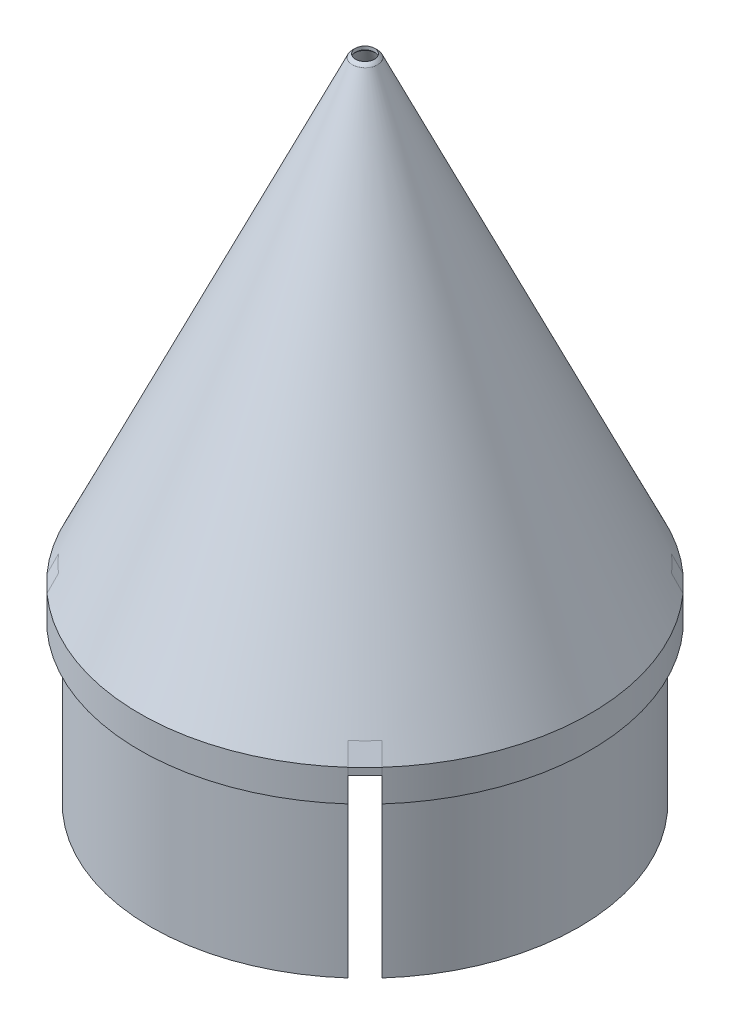
SolidWorks part; units mm, degrees
ref_plane "Front Plane" through (0, 0, 0) normal (0, 0, 1) x (1, 0, 0)
ref_plane "Top Plane" through (0, 0, 0) normal (0, 1, 0) x (1, 0, 0)
ref_plane "Right Plane" through (0, 0, 0) normal (1, 0, 0) x (0, 0, -1)
sketch "Sketch3" plane through (0, 0, 0) normal (0, 0, 1) x (1, 0, 0)
  line L1 (0, 0) -> (0, 155.682)
  line L4 (0, 0) -> (0, -50)
  line L5 (0, -50) -> (67.5, -50)
  line L6 (67.5, -50) -> (67.5, 0)
  line L9 (71, 0) -> (71, 10)
  line L11 (67.5, 0) -> (71, 0)
  line L12 (4, 153.682) -> (71, 10)
  line L13 (0, 229.1763) -> (0, 65.794) construction
  arc A0 (0, 155.682) -> (4, 153.682) centre (0, 150.682) cw
  point P11 (67.5, -50)
  point P14 (71, 10)
  dimension "Round yDim" = 2
  dimension "Lip Height" = 10
  dimension "Shoulder Height" = 50
  dimension "Half Angle" = 25
  dimension "Shoulder Diam" = 135
  dimension "Outer Diam" = 142
  dimension "Round xDim" = 8
revolve "Revolve1" add sketch "Sketch3" angle 360 about L1
shell "Shell1" thickness 0.8 removed face at (0, -50, -67.5)
sketch "Sketch7" plane through (0, 0, 0) normal (0, 1, 0) x (1, 0, 0)
  circle A0 centre (0, 0) radius 3
  dimension "PitotHoleDiam" = 6
extrude "Cut-Extrude3" cut sketch "Sketch7" along normal through all
ref_plane "Plane1" through (0, 0, 0) normal (1, 0, 0) x (0, 0, -1)
sketch "Sketch8" plane through (0, 0, 0) normal (1, 0, 0) x (0, 0, -1)
  line L0 (-39.807, 40.9099) -> (-39.807, 20) construction
  line L1 (-44.807, 44.0901) -> (-44.807, 39.0901) construction
  line L2 (-44.807, 39.0901) -> (-39.807, 40.9099) construction
  line L3 (-39.807, 40.9099) -> (-39.807, 35.9099)
  line L4 (-44.807, 44.0901) -> (-44.807, 39.0901)
  line L5 (-44.807, 39.0901) -> (-39.807, 40.9099)
  line L6 (-39.807, 35.9099) -> (-44.807, 34.0901)
  line L7 (-44.807, 34.0901) -> (-58.8839, 34.0901)
  line L8 (-3.3116, 153.2652) -> (-70.2, 9.8226) construction
  line L9 (-58.8839, 34.0901) -> (-44.807, 64.2781)
  line L10 (-44.807, 64.2781) -> (-44.807, 44.0901)
  dimension "D1" = 5
extrude "Boss-Extrude1" add sketch "Sketch8" along normal mid plane 15
sketch "Sketch9" plane through (0, 0, 0) normal (1, 0, 0) x (0, 0, -1)
  line L0 (-44.807, 39.0901) -> (-44.807, 62.9414) construction
  line L1 (-39.807, 40.9099) -> (-44.807, 39.0901) construction
  line L2 (-39.807, 35.9099) -> (-39.807, 40.9099) construction
  line L3 (-44.807, 34.0901) -> (-39.807, 35.9099) construction
  line L5 (-44.807, 39.0901) -> (-44.807, 62.9414)
  line L6 (-39.807, 40.9099) -> (-44.807, 39.0901)
  line L7 (-39.807, 35.9099) -> (-39.807, 40.9099)
  line L8 (-44.807, 34.0901) -> (-39.807, 35.9099)
  line L9 (-58.8839, 34.0901) -> (-44.807, 34.0901)
  line L10 (-44.807, 34.0901) -> (-44.807, 39.0901) construction
  line L11 (-44.807, 62.9414) -> (-58.8839, 34.0901)
extrude "Cut-Extrude4" cut sketch "Sketch9" against normal mid plane 3.5
pattern_circular "CirPattern1" count 2 over 360 about axis through (0, 0, 0) along (0, -1, 0) of "Boss-Extrude1", "Cut-Extrude4"
ref_axis "Axis1" through (0, 0, 0) along (0, -1, 0)
ref_plane "Plane2" through (0, 0, 0) normal (0.7071, 0, 0.7071) x (0, -1, 0)
sketch "Sketch11" plane through (0, 0, 0) normal (0.7071, 0, 0.7071) x (0, -1, 0)
  line L0 (-12.58, 59.0623) -> (-16.4367, 63.6586) construction
  line L1 (-16.4367, 63.6586) -> (-1.1158, 76.5143) construction
  line L2 (-1.1158, 76.5143) -> (2.7409, 71.9181) construction
  line L3 (2.7409, 71.9181) -> (-12.58, 59.0623) construction
  line L4 (-14.5083, 61.3604) -> (0.8126, 74.2162) construction
  line L5 (-8.0805, 66.7) -> (-0.8, 66.7) construction
  line L6 (-15.3609, 53.7) -> (-15.3609, 67.3869)
  line L7 (-15.3609, 67.3869) -> (-9.8226, 70.2)
  line L8 (-8.0805, 53.7) -> (-13.9678, 65.2905) construction
  line L9 (-13.9678, 65.2905) -> (-15.0999, 67.5194) construction
  line L10 (-9.8226, 70.2) -> (-153.9335, -3) construction
  line L11 (-9.8226, 70.2) -> (-0.8, 70.2)
  line L15 (0, 0) -> (50, 0) construction
  line L16 (-0.8, 53.7) -> (-0.8, 66.7)
  line L17 (-0.8, 66.7) -> (-0.8, 70.2)
  circle A2 centre (-8.0805, 53.7) radius 13 construction
  circle A3 centre (-8.0805, 53.7) radius 10 construction
  arc A4 (-15.3609, 53.7) -> (-0.8, 53.7) centre (-8.0805, 53.7) ccw
  point P6 (-14.5083, 61.3604)
  dimension "Arm Wheel Diam Mock" = 20
  dimension "D4" = 2.5
  dimension "Arm Wheel Arm Width Mock" = 6
  dimension "Arm Wheel Arm Length Mock" = 20
  dimension "ArmAngle" = 40
extrude "Boss-Extrude3" add sketch "Sketch11" along normal mid plane 20
sketch "Sketch13" plane through (0, -50, 0) normal (0, -1, 0) x (1, 0, 0)
  line L0 (39.8946, -25.7525) -> (25.7525, -39.8946) construction
  line L1 (30.1719, -35.4752) -> (35.4752, -30.1719)
  line L2 (30.1719, -35.4752) -> (47.4829, -52.7862)
  line L3 (35.4752, -30.1719) -> (52.7862, -47.4829)
  arc A0 (47.4829, -52.7862) -> (52.7862, -47.4829) centre (0, 0) ccw
  circle A1 centre (0, 0) radius 71 construction
  point P11 (32.8236, -32.8236)
  point P12 (32.8236, -32.8236)
  dimension "ArmCutoutWidth" = 7.5
extrude "Cut-Extrude8" cut sketch "Sketch13" against normal blind 65.5
hole_wizard "M4 Clearance Hole1" positions "Sketch14" profile "Sketch15" hole size "M4" standard "ANSI Metric"
sketch "Sketch14" plane through (7.0711, 0, 7.0711) normal (0.7071, 0, 0.7071) x (0.7071, 0, -0.7071)
  arc A0 (53.7, 15.3609) -> (53.7, 0.8) centre (53.7, 8.0805) ccw construction
  point P0 (53.7, 8.0805)
sketch "Sketch15" plane through (45.0427, 8.0805, -30.9006) normal (0, 1, 0) x (0.7071, 0, -0.7071)
  line L0 (0, 0) -> (0, 21.4421)
  line L1 (0, 21.4421) -> (2.4, 20)
  line L2 (2.4, 20) -> (2.4, 0)
  line L5 (2.4, 0) -> (0, 0)
  line L10 (0, 21.4421) -> (-2.4, 20) construction
  line L11 (0, -6.35) -> (0, 107.95) construction
  dimension "Hole Dia." = 4.8
  dimension "Hole Depth" = 20
  dimension "Drill Angle" = 118
sketch "Sketch17" plane through (0, 0, 0) normal (0.7071, 0, 0.7071) x (0, -1, 0)
  line L0 (-15.5, 67.5526) -> (-153.2652, 3.3116) construction
  line L1 (-48.9892, 51.9363) -> (-47.1766, 52.7816)
  line L8 (-48.9892, 51.9363) -> (-48.0732, 49.972)
  line L9 (-47.1766, 52.7816) -> (-46.2606, 50.8172)
  arc A0 (-48.0732, 49.972) -> (-46.2606, 50.8172) centre (-47.1669, 50.3946) ccw
  circle A1 centre (-47.1669, 50.3946) radius 0.25
  dimension "D1" = 1
  dimension "D2" = 0.5
extrude "Boss-Extrude4" add sketch "Sketch17" along normal mid plane 2.5
sketch "Sketch19" plane through (-7.0711, 0, -7.0711) normal (-0.7071, 0, -0.7071) x (-0.7071, 0, 0.7071)
  line L0 (-53.7, 8.0805) -> (-44.7, 8.0805) construction
  line L1 (-44.7, 12.8305) -> (-48.1825, 12.8305)
  line L2 (-44.7, 3.3305) -> (-48.1825, 3.3305)
  arc A0 (-53.7, 0.8) -> (-53.7, 15.3609) centre (-53.7, 8.0805) ccw construction
  arc A1 (-48.1825, 3.3305) -> (-48.1825, 12.8305) centre (-53.7, 8.0805) ccw
  circle A2 centre (-44.7, 8.0805) radius 2.75 construction
  arc A3 (-44.7, 3.3305) -> (-44.7, 12.8305) centre (-44.7, 8.0805) ccw
  dimension "D1" = 5.5
  dimension "D2" = 2
  dimension "D3" = 9
extrude "Boss-Extrude7" add sketch "Sketch19" against normal blind 6.25
sketch "Sketch21" plane through (-7.0711, 0, -7.0711) normal (-0.7071, 0, -0.7071) x (-0.7071, 0, 0.7071)
  circle A0 centre (-44.7, 8.0805) radius 2.8
  arc A1 (-44.7, 3.3305) -> (-44.7, 12.8305) centre (-44.7, 8.0805) ccw construction
  dimension "D1" = 5.6
extrude "Cut-Extrude9" cut sketch "Sketch21" against normal up to next
sketch "Sketch22" plane through (-7.0711, 0, -7.0711) normal (-0.7071, 0, -0.7071) x (-0.7071, 0, 0.7071)
  circle A0 centre (-44.7, 8.0805) radius 4.75
  arc A1 (-44.7, 3.3305) -> (-44.7, 12.8305) centre (-44.7, 8.0805) ccw construction
  circle A2 centre (-44.7, 8.0805) radius 2.8 construction
  circle A3 centre (-44.7, 8.0805) radius 2.8
extrude "Boss-Extrude8" add sketch "Sketch22" along normal blind 4
sketch "Sketch23" plane through (-9.8995, 0, -9.8995) normal (-0.7071, 0, -0.7071) x (-0.7071, 0, 0.7071)
  circle A0 centre (-44.7, 8.0805) radius 4.75 construction
  circle A1 centre (-44.7, 8.0805) radius 4.75
  circle A2 centre (-44.7, 8.0805) radius 2.3
  dimension "D1" = 4.6
extrude "Boss-Extrude9" add sketch "Sketch23" along normal blind 2
pattern_circular "CirPattern4" count 4 over 360 about axis through (0, 0, 0) along (0, -1, 0) of "M4 Clearance Hole1", "Boss-Extrude3", "Boss-Extrude4", "Cut-Extrude8", "Boss-Extrude7", "Cut-Extrude9", "Boss-Extrude8", "Boss-Extrude9"
sketch "Sketch18" plane through (1.9445, 0, -7.2478) normal (0.7071, 0, 0.7071) x (0.7071, 0, -0.7071)
  line L0 (61.8325, 15.5) -> (64.4009, 10)
  line L1 (64.4009, 10) -> (64.4009, 7.8056)
  line L2 (64.4009, 10) -> (64.4009, 0) construction
  line L3 (64.4009, 7.8056) -> (62.5843, 9.9705)
  line L6 (60.9484, 15.5) -> (61.8325, 15.5)
  line L7 (62.5843, 9.9705) -> (62.5843, 5.3699) construction
  circle A1 centre (47.2, 8.0805) radius 15 construction
  circle A3 centre (47.2, 8.0805) radius 2.4 construction
  arc A4 (58.8643, 16.7375) -> (57.751, 18.0643) centre (57.9246, 17.0795) ccw construction
  arc A6 (62.5843, 9.9705) -> (60.9484, 15.5) centre (52.4213, 9.9705) ccw
  dimension "D1" = 15
  dimension "D2" = 13
  dimension "ArmStopperAngle" = 40
  dimension "D4" = 15.5
extrude "Boss-Extrude6" add sketch "Sketch18" along normal up to next
pattern_circular "CirPattern8" count 4 over 360 about axis through (0, 0, 0) along (0, -1, 0) of "Boss-Extrude6"
equation "\"LegAngle\"=30"
